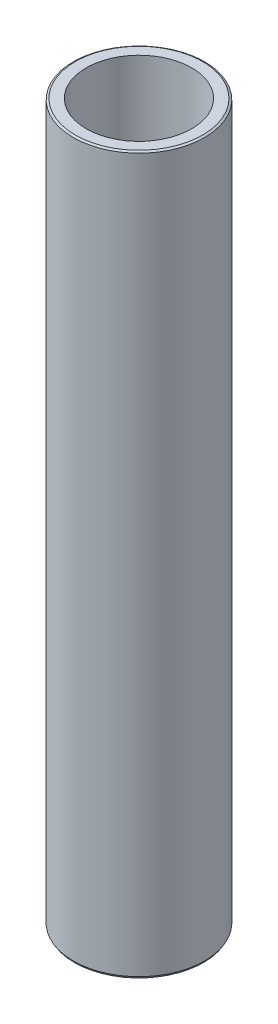
SolidWorks part; units mm, degrees
ref_plane "Front Plane" through (0, 0, 0) normal (0, 0, 1) x (1, 0, 0)
ref_plane "Top Plane" through (0, 0, 0) normal (0, 1, 0) x (1, 0, 0)
ref_plane "Right Plane" through (0, 0, 0) normal (1, 0, 0) x (0, 0, -1)
sketch "Sketch1" plane through (0, 0, 0) normal (0, 1, 0) x (1, 0, 0)
  circle A0 centre (0, 0) radius 55
  dimension "SHAFT_OD" = 110
extrude "Boss-Extrude1" add sketch "Sketch1" along normal blind 600
sketch "Sketch2" plane through (0, 0, 0) normal (0, 1, 0) x (1, 0, 0)
  circle A0 centre (0, 0) radius 44.2155
  dimension "BORE_D" = 88.431
extrude "Cut-Extrude1" cut sketch "Sketch2" along normal through all
chamfer "Chamfer1" distance 0.9524 angle 60 2 edges at (0, 600, 55) (0, 0, 55) first distance on face at (0, 600, 55) first distance on face at (0, 0, 44.2155)
